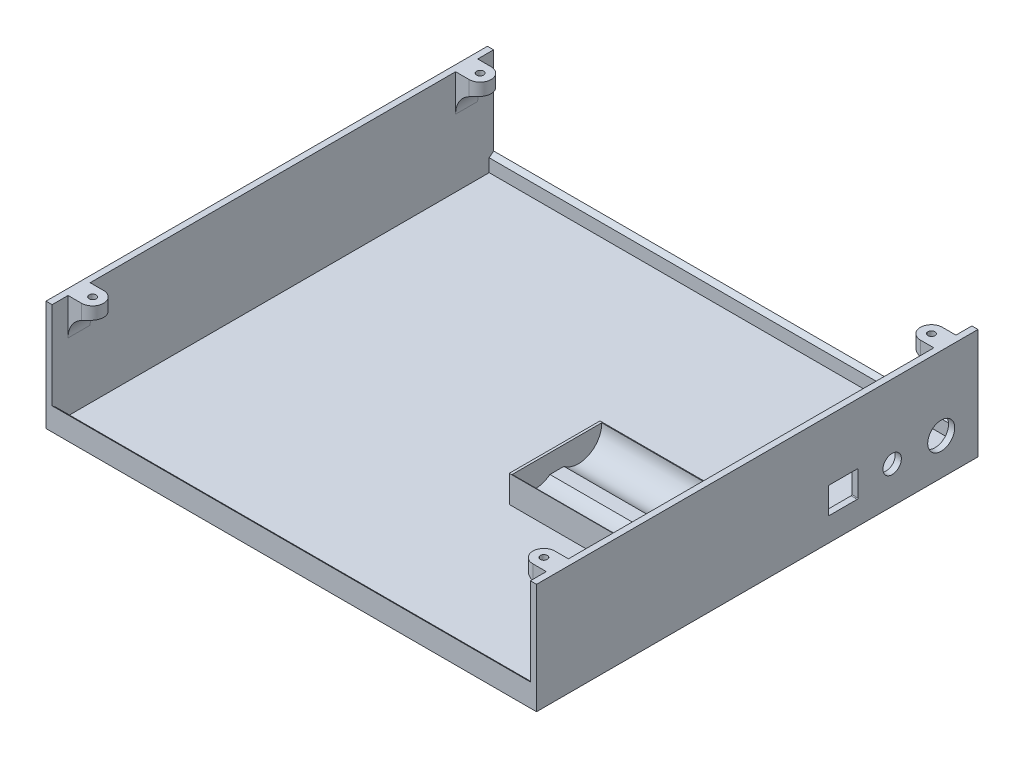
SolidWorks part; units mm, degrees
material "PLA"
ref_plane "Alzado" through (0, 0, 0) normal (0, 0, 1) x (1, 0, 0)
ref_plane "Planta" through (0, 0, 0) normal (0, 1, 0) x (1, 0, 0)
ref_plane "Vista lateral" through (0, 0, 0) normal (1, 0, 0) x (0, 0, -1)
sketch "Croquis1" plane through (0, 0, 0) normal (1, 0, 0) x (0, 0, -1)
  line L0 (90, 9.274) -> (90, 0)
  line L1 (90, 0) -> (-90, 0)
  line L2 (90, 9.274) -> (88.2, 7.7666)
  line L3 (88.2, 7.7666) -> (88.2, 2.5)
  line L4 (88.2, 2.5) -> (-88.2, 2.5)
  line L5 (0, 2.5) -> (0, 0) construction
  line L6 (-88.2, 7.7666) -> (-88.2, 2.5)
  line L7 (-90, 9.274) -> (-88.2, 7.7666)
  line L8 (-90, 9.274) -> (-90, 0)
  dimension "D1" = 2.5
  dimension "D2" = 90
  dimension "D3" = 9.274
  dimension "D4" = 2.3478
  dimension "D5" = 5.2666
extrude "Saliente-Extruir1" add sketch "Croquis1" along normal blind 200
sketch "Croquis2" plane through (0, 2.5, 0) normal (0, 1, 0) x (1, 0, 0)
  line L1 (197.5, 90) -> (200, 90)
  line L2 (197.5, 90) -> (197.5, -90)
  line L3 (197.5, -90) -> (200, -90)
  line L4 (200, 90) -> (200, -90)
  line L5 (197.5, 90) -> (200, -90) construction
  line L6 (197.5, -90) -> (200, 90) construction
  line L9 (200, 90) -> (0, 90) construction
  line L10 (200, -90) -> (0, -90) construction
  line L11 (200, 88.2) -> (200, -88.2) construction
  line L12 (0, 88.2) -> (0, -88.2) construction
  line L13 (0, 90) -> (2.5, 90)
  line L14 (0, 90) -> (0, -90)
  line L15 (0, -90) -> (2.5, -90)
  line L16 (2.5, 90) -> (2.5, -90)
  line L17 (0, 90) -> (2.5, -90) construction
  line L18 (0, -90) -> (2.5, 90) construction
  point P0 (198.75, 0)
  point P11 (1.25, 0)
  dimension "D1" = 2.5
  dimension "D2" = 2.5
extrude "Saliente-Extruir2" add sketch "Croquis2" along normal blind 42.5
sketch "Croquis3" plane through (200, 0, 0) normal (1, 0, 0) x (0, 0, -1)
  line L0 (-90, 0) -> (90, 0) construction
  line L1 (90, 0) -> (90, 45) construction
  circle A0 centre (75, 15) radius 5.5
  dimension "D1" = 11
  dimension "D2" = 15
  dimension "D3" = 15
extrude "Cortar-Extruir1" cut sketch "Croquis3" against normal blind 4
sketch "Croquis4" plane through (200, 0, 0) normal (1, 0, 0) x (0, 0, -1)
  line L0 (90, 0) -> (90, 45) construction
  line L1 (-90, 0) -> (90, 0) construction
  circle A0 centre (55, 15) radius 3.75
  dimension "D1" = 7.5
  dimension "D2" = 35
  dimension "D3" = 15
extrude "Cortar-Extruir2" cut sketch "Croquis4" against normal blind 4
sketch "Croquis7" plane through (200, 0, 0) normal (1, 0, 0) x (0, 0, -1)
  line L0 (-90, 0) -> (90, 0) construction
  line L1 (28.95, 20.375) -> (41.05, 20.375)
  line L2 (28.95, 20.375) -> (28.95, 9.625)
  line L3 (28.95, 9.625) -> (41.05, 9.625)
  line L4 (41.05, 20.375) -> (41.05, 9.625)
  line L5 (28.95, 20.375) -> (41.05, 9.625) construction
  line L6 (28.95, 9.625) -> (41.05, 20.375) construction
  line L7 (90, 0) -> (90, 45) construction
  point P0 (35, 15)
  dimension "D1" = 10.75
  dimension "D2" = 12.1
  dimension "D3" = 15
  dimension "D4" = 55
extrude "Cortar-Extruir3" cut sketch "Croquis7" against normal blind 4
fillet "Redondeo1" radius 0.3 4 edges at (198.75, 9.625, -41.05) (198.75, 9.625, -28.95) (198.75, 20.375, -41.05) (198.75, 20.375, -28.95)
sketch "Croquis8" plane through (0, 45, 0) normal (0, 1, 0) x (1, 0, 0)
  line L0 (192, -74.5067) -> (197.5, -74.5067)
  line L1 (197.5, 90) -> (197.5, -90) construction
  line L2 (192, -83.5067) -> (197.5, -83.5067)
  line L3 (197.5, -83.5067) -> (197.5, -74.5067)
  arc A0 (192, -74.5067) -> (192, -83.5067) centre (192, -79.0067) ccw
  circle A1 centre (192, -79.0067) radius 1.425
  dimension "D1" = 10
  dimension "D2" = 9
  dimension "D3" = 2.85
extrude "Saliente-Extruir3" add sketch "Croquis8" against normal blind 5
mirror "Simetría1" about plane through (0, 0, 0) normal (0, 0, 1) of "Saliente-Extruir3"
ref_plane "Plano1" through (100, 0, 0) normal (1, 0, 0) x (0, 0, -1)
mirror "Simetría2" about plane through (100, 0, 0) normal (1, 0, 0) of "Simetría1"
fillet "Redondeo4" radius 10 2 edges at (197.5, 40, 79.0067) (197.5, 40, -79.0067)
fillet "Redondeo5" radius 10 2 edges at (2.5, 40, -79.0067) (2.5, 40, 79.0067)
sketch "Croquis9" plane through (0, 2.5, 0) normal (0, 1, 0) x (1, 0, 0)
  line L1 (190.7398, -24.8534) -> (123.7398, -24.8534)
  line L2 (190.7398, -24.8534) -> (190.7398, 12.1466)
  line L3 (190.7398, 12.1466) -> (123.7398, 12.1466)
  line L4 (123.7398, -24.8534) -> (123.7398, 12.1466)
  line L5 (190.7398, -24.8534) -> (123.7398, 12.1466) construction
  line L6 (190.7398, 12.1466) -> (123.7398, -24.8534) construction
  point P0 (157.2398, -6.3534)
  dimension "D1" = 37
  dimension "D2" = 67
extrude "Saliente-Extruir4" add sketch "Croquis9" along normal blind 20
sketch "Croquis10" plane through (190.7398, 0, 0) normal (1, 0, 0) x (0, 0, -1)
  arc A0 (-6.4201, 16.9309) -> (-6.4201, 9.5637) centre (-15.1769, 13.2473) ccw
  arc A1 (-6.4201, 9.5637) -> (-6.4201, 16.9309) centre (2.3367, 13.2473) ccw
  dimension "D1" = 19
  dimension "D2" = 19
extrude "Cortar-Extruir5" cut sketch "Croquis10" against normal blind 66 and the other way blind 1
sketch "Croquis11" plane through (0, 22.5, 0) normal (0, 1, 0) x (1, 0, 0)
  line L1 (192.0328, 13.1316) -> (122.4467, 13.1316)
  line L2 (192.0328, 13.1316) -> (192.0328, -25.8384)
  line L3 (192.0328, -25.8384) -> (122.4467, -25.8384)
  line L4 (122.4467, 13.1316) -> (122.4467, -25.8384)
  line L5 (192.0328, 13.1316) -> (122.4467, -25.8384) construction
  line L6 (192.0328, -25.8384) -> (122.4467, 13.1316) construction
  point P0 (157.2398, -6.3534)
extrude "Cortar-Extruir6" cut sketch "Croquis11" against normal blind 9
sketch "Croquis12" plane through (190.7398, 0, 0) normal (1, 0, 0) x (0, 0, -1)
  line L0 (12.1466, 13.5) -> (12.1466, 2.5) construction
  line L1 (-24.8534, 2.5) -> (12.1466, 2.5)
  line L2 (-24.8534, 2.5) -> (-24.8534, 13.4977)
  line L3 (-24.8534, 13.4977) -> (12.1466, 13.4977)
  line L4 (12.1466, 2.5) -> (12.1466, 13.4977)
  line L5 (-24.8534, 2.5) -> (12.1466, 13.4977) construction
  line L6 (-24.8534, 13.4977) -> (12.1466, 2.5) construction
  line L7 (-24.8534, 13.5) -> (-24.8534, 2.5) construction
  line L8 (-24.8534, 2.5) -> (12.1466, 2.5) construction
  point P0 (-6.3534, 7.9989)
extrude "Saliente-Extruir5" add sketch "Croquis12" along normal blind 0.7 contours L3 L4 L1 L2
sketch "Croquis14" plane through (0, 13.4977, 0) normal (0, 1, 0) x (1, 0, 0)
  line L0 (190.7398, -6.4201) -> (124.7398, -6.4201) construction
  line L1 (124.7398, -2.8927) -> (190.7398, -2.8927)
  line L2 (124.7398, -2.8927) -> (124.7398, -9.9474)
  line L3 (124.7398, -9.9474) -> (190.7398, -9.9474)
  line L4 (190.7398, -2.8927) -> (190.7398, -9.9474)
  line L5 (124.7398, -2.8927) -> (190.7398, -9.9474) construction
  line L6 (124.7398, -9.9474) -> (190.7398, -2.8927) construction
  line L7 (190.7398, -6.4201) -> (190.7398, -24.6769) construction
  point P0 (157.7398, -6.4201)
extrude "Cortar-Extruir7" cut sketch "Croquis14" against normal blind 7.7
